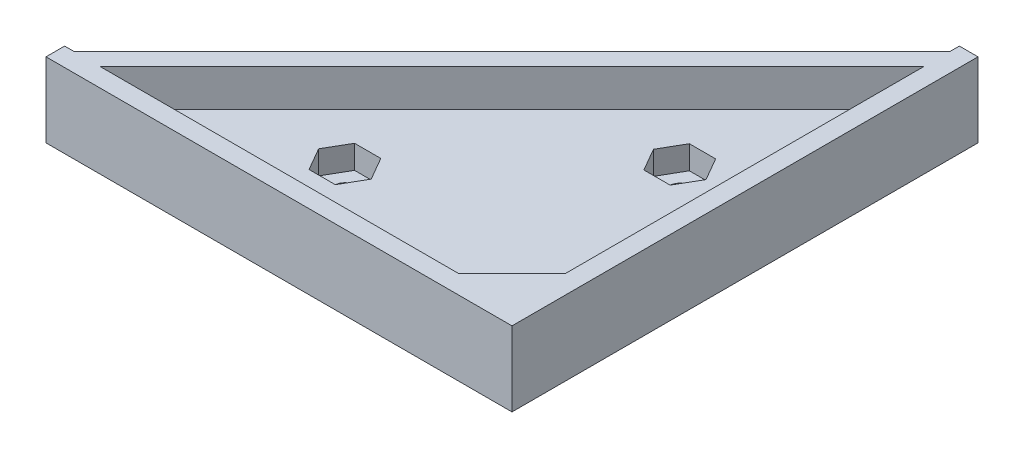
SolidWorks part; units mm, degrees
ref_plane "Front Plane" through (0, 0, 0) normal (0, 0, 1) x (1, 0, 0)
ref_plane "Top Plane" through (0, 0, 0) normal (0, 1, 0) x (1, 0, 0)
ref_plane "Right Plane" through (0, 0, 0) normal (1, 0, 0) x (0, 0, -1)
sketch "Sketch1" plane through (0, 0, 0) normal (0, 1, 0) x (1, 0, 0)
  line L0 (-79.375, 0) -> (0, 0)
  line L1 (0, 0) -> (0, 79.375)
  line L2 (0, 79.375) -> (-3.175, 79.375)
  line L3 (-3.175, 79.375) -> (-3.175, 77.7875)
  line L4 (-3.175, 77.7875) -> (-77.7875, 3.175)
  line L5 (-77.7875, 3.175) -> (-79.375, 3.175)
  line L6 (-79.375, 3.175) -> (-79.375, 0)
  dimension "D1" = 76.2
  dimension "D2" = 79.375
  dimension "D3" = 3.175
  dimension "D4" = 1.5875
extrude "Boss-Extrude1" add sketch "Sketch1" along normal blind 12.7
sketch "Sketch2" plane through (0, 12.7, 0) normal (0, 1, 0) x (1, 0, 0)
  line L0 (-73.2974, 3.175) -> (-12.2411, 3.175)
  line L1 (-3.175, 12.2411) -> (-3.175, 73.2974)
  line L2 (-3.175, 73.2974) -> (-73.2974, 3.175)
  line L3 (-12.2411, 3.175) -> (-3.175, 12.2411)
  line L5 (-79.375, 0) -> (0, 0) construction
  line L6 (0, 0) -> (0, 79.375) construction
  line L7 (-3.175, 77.7875) -> (-77.7875, 3.175) construction
  dimension "D2" = 3.175
  dimension "D3" = 3.175
  dimension "D4" = 3.175
extrude "Cut-Extrude1" cut sketch "Sketch2" against normal blind 6.35
chamfer "Chamfer1" distance 6.35 angle 45 1 edges at (-7.708, 6.35, -7.708)
sketch "Sketch3" plane through (0, 6.35, 0) normal (0, 1, 0) x (1, 0, 0)
  line L0 (-79.375, 0) -> (0, 0) construction
  line L1 (0, 0) -> (0, 79.375) construction
  circle A0 centre (-44.4608, 16.002) radius 1.75
  circle A1 centre (-15.875, 44.45) radius 1.75
  dimension "D1" = 3.5
  dimension "D2" = 3.5
  dimension "D3" = 16.002
  dimension "D4" = 44.4608
  dimension "D5" = 15.875
  dimension "D6" = 44.45
extrude "Cut-Extrude2" cut sketch "Sketch3" against normal blind 6.35
sketch "Sketch4" plane through (0, 6.35, 0) normal (0, 1, 0) x (1, 0, 0)
  line L1 (-13.6378, 40.575) -> (-11.4005, 44.45)
  line L2 (-11.4005, 44.45) -> (-13.6378, 48.325)
  line L3 (-13.6378, 48.325) -> (-18.1122, 48.325)
  line L4 (-18.1122, 48.325) -> (-20.3495, 44.45)
  line L5 (-20.3495, 44.45) -> (-18.1122, 40.575)
  line L6 (-18.1122, 40.575) -> (-13.6378, 40.575)
  line L7 (-39.9863, 16.002) -> (-42.2236, 19.877)
  line L8 (-42.2236, 19.877) -> (-46.698, 19.877)
  line L9 (-46.698, 19.877) -> (-48.9353, 16.002)
  line L10 (-48.9353, 16.002) -> (-46.698, 12.127)
  line L11 (-46.698, 12.127) -> (-42.2236, 12.127)
  line L12 (-42.2236, 12.127) -> (-39.9863, 16.002)
  circle A0 centre (-44.4608, 16.002) radius 1.75 construction
  circle A1 centre (-15.875, 44.45) radius 1.75 construction
  circle A2 centre (-44.4608, 16.002) radius 1.75
  circle A3 centre (-15.875, 44.45) radius 1.75
  circle A4 centre (-15.875, 44.45) radius 3.875 construction
  circle A5 centre (-44.4608, 16.002) radius 3.875 construction
  dimension "D1" = 7.75
  dimension "D2" = 7.75
extrude "Cut-Extrude3" cut sketch "Sketch4" against normal blind 4
